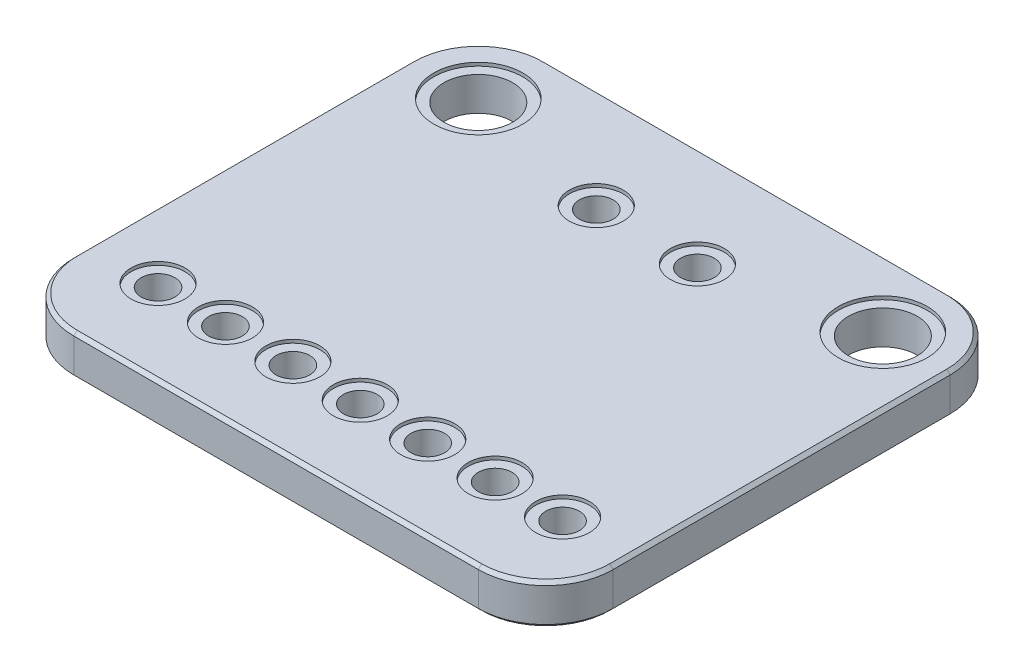
SolidWorks part; units mm, degrees
ref_plane "Front Plane" through (0, 0, 0) normal (0, 0, 1) x (1, 0, 0)
ref_plane "Top Plane" through (0, 0, 0) normal (0, 1, 0) x (1, 0, 0)
ref_plane "Right Plane" through (0, 0, 0) normal (1, 0, 0) x (0, 0, -1)
sketch "Sketch1" plane through (0, 0, 0) normal (0, 1, 0) x (1, 0, 0)
  line L1 (-7.62, -8.89) -> (7.62, -8.89)
  line L2 (-10.16, -6.35) -> (-10.16, 6.35)
  line L3 (-7.62, 8.89) -> (7.62, 8.89)
  line L4 (10.16, -6.35) -> (10.16, 6.35)
  arc A0 (-7.62, -8.89) -> (-10.16, -6.35) centre (-7.62, -6.35) cw
  arc A1 (7.62, -8.89) -> (10.16, -6.35) centre (7.62, -6.35) ccw
  arc A2 (7.62, 8.89) -> (10.16, 6.35) centre (7.62, 6.35) cw
  arc A3 (-10.16, 6.35) -> (-7.62, 8.89) centre (-7.62, 6.35) cw
  point P4 (-10.16, 0)
  point P6 (0, -8.89)
  point P9 (-10.16, -8.89)
  point P14 (10.16, 8.89)
  point P17 (-10.16, 8.89)
  dimension "D3" = 2.54
  dimension "D1" = 20.32
  dimension "D2" = 17.78
extrude "Boss-Extrude1" add sketch "Sketch1" along normal blind 1.524
ref_plane "Plane1" through (0, 0.762, 0) normal (0, 1, 0) x (1, 0, 0)
sketch "Sketch2" plane through (0, 1.524, 0) normal (0, 1, 0) x (1, 0, 0)
  line L0 (-1.905, 5.08) -> (1.905, 5.08) construction
  line L1 (-7.62, -5.715) -> (-5.08, -5.715) construction
  line L2 (-5.08, -5.715) -> (-2.54, -5.715) construction
  line L3 (-2.54, -5.715) -> (0, -5.715) construction
  line L4 (0, -5.715) -> (2.54, -5.715) construction
  line L5 (2.54, -5.715) -> (5.08, -5.715) construction
  line L6 (5.08, -5.715) -> (7.62, -5.715) construction
  line L8 (-7.62, -8.89) -> (7.62, -8.89)
  line L9 (10.16, -6.35) -> (10.16, 6.35)
  line L10 (7.62, 8.89) -> (-7.62, 8.89)
  line L11 (-10.16, 6.35) -> (-10.16, -6.35)
  line L12 (-7.62, -8.89) -> (7.62, -8.89)
  line L13 (10.16, -6.35) -> (10.16, 6.35)
  line L14 (7.62, 8.89) -> (-7.62, 8.89)
  line L15 (-10.16, 6.35) -> (-10.16, -6.35)
  circle A0 centre (-7.62, 6.35) radius 1.294
  circle A1 centre (7.62, 6.35) radius 1.294
  circle A4 centre (-7.62, 6.35) radius 1.675
  circle A5 centre (7.62, 6.35) radius 1.675
  arc A8 (-10.16, -6.35) -> (-7.62, -8.89) centre (-7.62, -6.35) ccw
  arc A9 (7.62, -8.89) -> (10.16, -6.35) centre (7.62, -6.35) ccw
  arc A10 (10.16, 6.35) -> (7.62, 8.89) centre (7.62, 6.35) ccw
  arc A11 (-7.62, 8.89) -> (-10.16, 6.35) centre (-7.62, 6.35) ccw
  arc A12 (-10.16, -6.35) -> (-7.62, -8.89) centre (-7.62, -6.35) ccw
  arc A13 (7.62, -8.89) -> (10.16, -6.35) centre (7.62, -6.35) ccw
  arc A14 (10.16, 6.35) -> (7.62, 8.89) centre (7.62, 6.35) ccw
  arc A15 (-7.62, 8.89) -> (-10.16, 6.35) centre (-7.62, 6.35) ccw
  circle A16 centre (-1.905, 5.08) radius 1.016
  circle A17 centre (-1.905, 5.08) radius 0.635
  circle A18 centre (1.905, 5.08) radius 0.635
  circle A19 centre (1.905, 5.08) radius 1.016
  circle A20 centre (-7.62, -5.715) radius 0.635
  circle A21 centre (-5.08, -5.715) radius 0.635
  circle A22 centre (-2.54, -5.715) radius 0.635
  circle A23 centre (0, -5.715) radius 0.635
  circle A24 centre (2.54, -5.715) radius 0.635
  circle A25 centre (5.08, -5.715) radius 0.635
  circle A26 centre (7.62, -5.715) radius 0.635
  circle A27 centre (-7.62, -5.715) radius 1.016
  circle A28 centre (-5.08, -5.715) radius 1.016
  circle A29 centre (-2.54, -5.715) radius 1.016
  circle A30 centre (0, -5.715) radius 1.016
  circle A31 centre (2.54, -5.715) radius 1.016
  circle A32 centre (5.08, -5.715) radius 1.016
  circle A33 centre (7.62, -5.715) radius 1.016
  point P16 (0, 5.08)
  point P17 (0, 8.89)
  dimension "D2" = 3.35
  dimension "D3" = 0.381
  dimension "D4" = 2.032
  dimension "D5" = 0.381
  dimension "D6" = 3.81
  dimension "D10" = 1.27
  dimension "D11" = 0.381
  dimension "D7" = 3.81
  dimension "D8" = 2.54
  dimension "D9" = 3.175
  dimension "D1" = 0
extrude "Cut-Extrude1" cut sketch "Sketch2" against normal blind 1.524 contours A0 | A1 | A20 | A21 | A22 | A23 | A24 | A25 | A26 | A18 | A17 region at (-7.62, 1.524, -6.35) region at (7.62, 1.524, -6.35)
extrude "Cut-Extrude2" cut sketch "Sketch2<4>" against normal blind 0.127 contours A4 A0 | A16 A17 | A19 A18 | A5 A1 | A33 A26 | A32 A25 | A31 A24 | A30 A23 | A29 A22 | A28 A21 | A27 A20 region at (-9.2476, 1.524, -6.35) region at (5.9924, 1.524, -6.35) region at (-2.8923, 1.524, -5.08) region at (0.9177, 1.524, -5.08) region at (-8.6073, 1.524, 5.715) region at (-6.0673, 1.524, 5.715) region at (-3.5273, 1.524, 5.715) region at (-0.9873, 1.524, 5.715) region at (1.5527, 1.524, 5.715) region at (4.0927, 1.524, 5.715) region at (6.6327, 1.524, 5.715)
sketch "Sketch2<4>" plane through (0, 1.524, 0) normal (0, 1, 0) x (1, 0, 0) same geometry as "Sketch2"
mirror "Mirror1" about plane through (0, 0.762, 0) normal (0, 1, 0) of "Cut-Extrude2"
chamfer "Chamfer1" distance 0.127 angle 45 16 edges at (10.16, 1.524, 0) (9.4161, 1.524, -8.1461) (9.4161, 1.524, 8.1461) (0, 1.524, -8.89) (0, 1.524, 8.89) (-9.4161, 1.524, -8.1461) (-9.4161, 1.524, 8.1461) (-10.16, 1.524, 0) (-9.4161, 0, -8.1461) (-10.16, 0, 0) (-9.4161, 0, 8.1461) (0, 0, 8.89) (9.4161, 0, 8.1461) (10.16, 0, 0) (9.4161, 0, -8.1461) (0, 0, -8.89)
